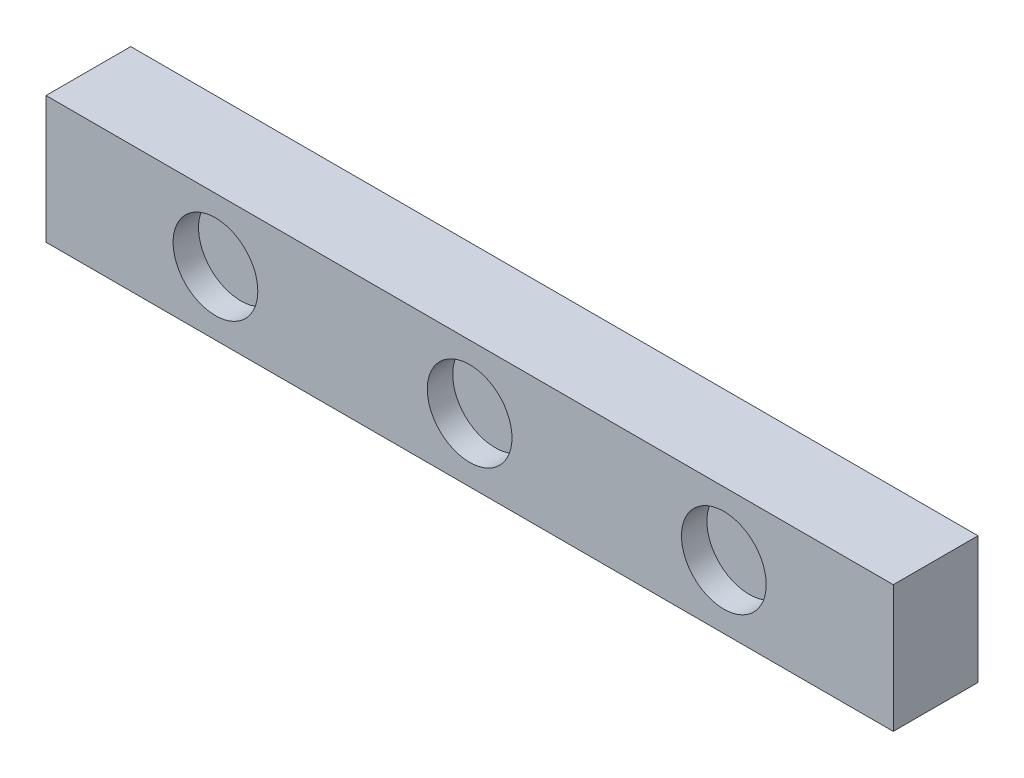
SolidWorks part; units mm, degrees
ref_plane "Front Plane" through (0, 0, 0) normal (0, 0, 1) x (1, 0, 0)
ref_plane "Top Plane" through (0, 0, 0) normal (0, 1, 0) x (1, 0, 0)
ref_plane "Right Plane" through (0, 0, 0) normal (1, 0, 0) x (0, 0, -1)
sketch "Sketch2" plane through (0, 0, 0) normal (0, 0, 1) x (1, 0, 0)
  line L1 (-500, 75) -> (500, 75)
  line L2 (-500, 75) -> (-500, -75)
  line L3 (-500, -75) -> (500, -75)
  line L4 (500, 75) -> (500, -75)
  circle A0 centre (0, 0) radius 50
  circle A1 centre (300, 0) radius 50
  circle A2 centre (-300, 0) radius 50
  point P0 (0, 0)
  dimension "D3" = 100
  dimension "D1" = 1000
  dimension "D2" = 150
  dimension "D4" = 300
  dimension "D5" = 200
  dimension "D6" = 200
  dimension "D7" = 75
extrude "Boss-Extrude2" add sketch "Sketch2" against normal blind 100 contours A2 | A0 | A1 | L4 L1 L2 L3 A2 A1 A0 region at (0, 64.8881, 0) region at (0, 0, 0) region at (300, 0, 0) region at (-300, 0, 0)
extrude "Cut-Extrude1" cut sketch "Sketch2<5>" against normal blind 30 contours A2 | A1 | A0 region at (300, 0, 0) region at (-300, 0, 0)
sketch "Sketch2<5>" plane through (0, 0, 0) normal (0, 0, 1) x (1, 0, 0) same geometry as "Sketch2"
